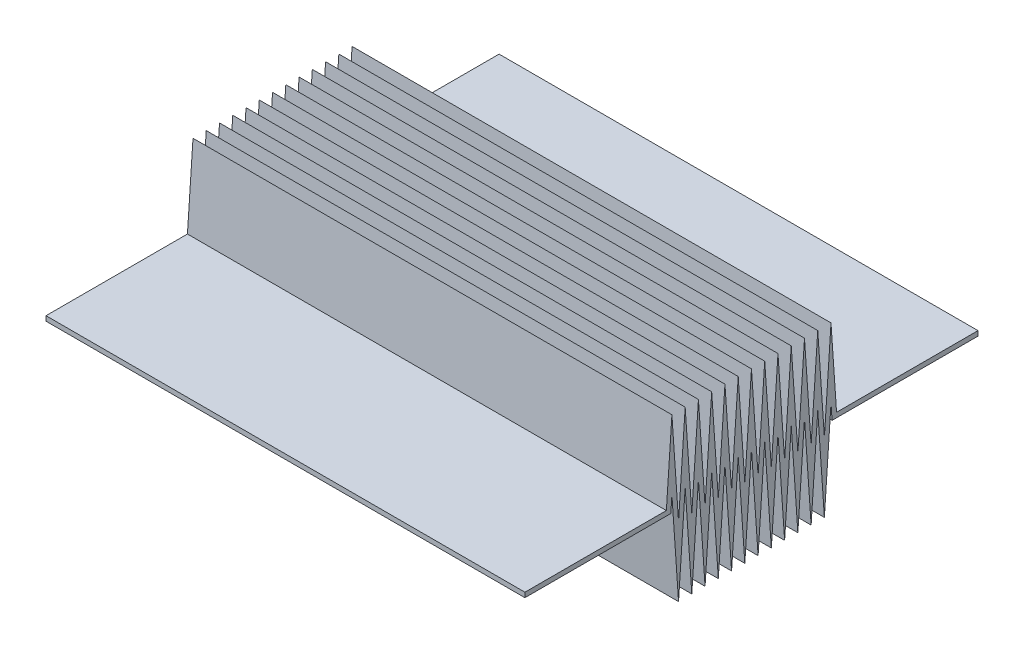
SolidWorks part; units mm, degrees
ref_plane "Front Plane" through (0, 0, 0) normal (0, 0, 1) x (1, 0, 0)
ref_plane "Top Plane" through (0, 0, 0) normal (0, 1, 0) x (1, 0, 0)
ref_plane "Right Plane" through (0, 0, 0) normal (1, 0, 0) x (0, 0, -1)
sketch "Sketch2" plane through (0, 0, 0) normal (0, 0, 1) x (1, 0, 0)
  line L1 (-27.5, 10) -> (27.5, 10)
  line L2 (-27.5, 10) -> (-27.5, 0)
  line L3 (-27.5, 0) -> (27.5, 0)
  line L4 (27.5, 10) -> (27.5, 0)
  point P4 (0, 0)
  dimension "D1" = 10
  dimension "D2" = 55
sketch "Sketch3" plane through (0, 0, 0) normal (1, 0, 0) x (0, 0, -1)
  line L0 (0, 10) -> (47.3022, 10) construction
  line L1 (0, 0) -> (47.3022, 0) construction
  line L3 (15, 5) -> (15.346, 10)
  line L4 (15.346, 10) -> (16.0381, 0)
  line L5 (16.0381, 0) -> (16.7302, 10)
  line L6 (16.7302, 10) -> (17.4223, 0)
  line L7 (17.4223, 0) -> (18.1144, 10)
  line L8 (18.1144, 10) -> (18.8065, 0)
  line L9 (18.8065, 0) -> (19.4986, 10)
  line L10 (19.4986, 10) -> (20.1907, 0)
  line L11 (20.1907, 0) -> (20.8828, 10)
  line L12 (20.8828, 10) -> (21.5748, 0)
  line L13 (21.5748, 0) -> (22.2669, 10)
  line L14 (22.2669, 10) -> (22.959, 0)
  line L15 (22.959, 0) -> (23.6511, 10)
  line L16 (23.6511, 10) -> (24.3432, 0)
  line L17 (24.3432, 0) -> (25.0353, 10)
  line L18 (25.0353, 10) -> (25.7274, 0)
  line L19 (0, 10) -> (0, 0) construction
  line L20 (25.7274, 0) -> (26.4195, 10)
  line L21 (26.4195, 10) -> (27.1116, 0)
  line L22 (27.1116, 0) -> (27.8036, 10)
  line L23 (27.8036, 10) -> (28.4957, 0)
  line L24 (28.4957, 0) -> (29.1878, 10)
  line L25 (29.1878, 10) -> (29.8799, 0)
  line L26 (29.8799, 0) -> (30.572, 10)
  line L27 (30.572, 10) -> (31.2641, 0)
  line L28 (31.2641, 0) -> (31.9562, 10)
  line L29 (31.9562, 10) -> (32.3022, 5)
  line L30 (47.3022, 10) -> (47.3022, 0) construction
  line L31 (15, 5) -> (0, 5)
  line L32 (32.3022, 5) -> (47.3022, 5)
  line L34 (47.3022, 4.75) -> (47.3022, 22.75) construction
  dimension "D2" = 15
  dimension "D1" = 10
  dimension "D3" = 15
extrude "Extrude-Thin1" add sketch "Sketch3" against normal mid plane 50 thin thin type mid plane wall 0.5
